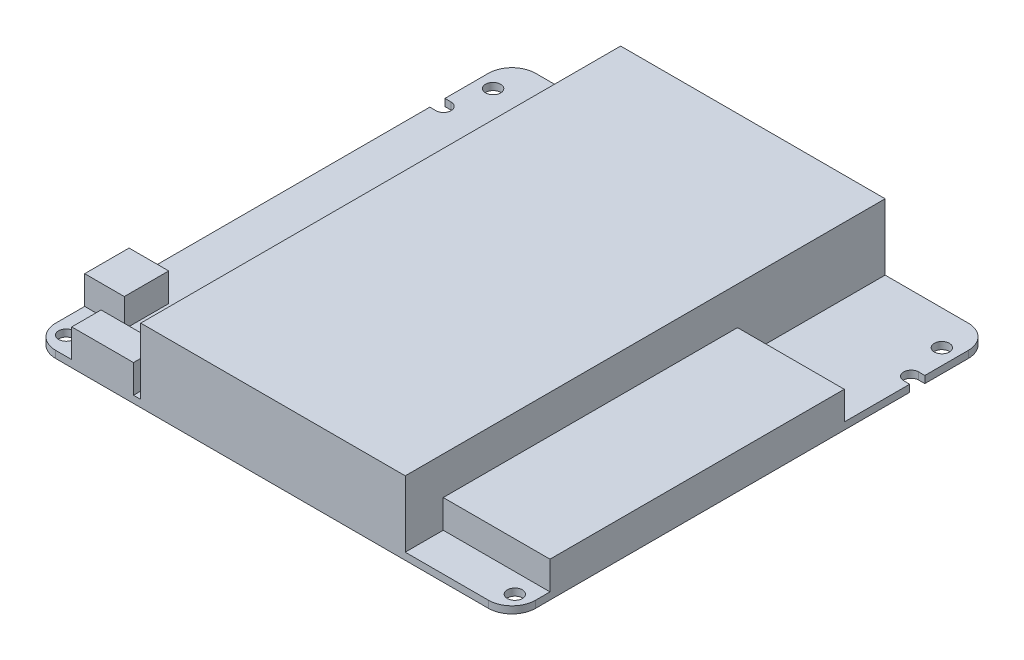
SolidWorks part; units mm, degrees
ref_plane "Спереди" through (0, 0, 0) normal (0, 0, 1) x (1, 0, 0)
ref_plane "Сверху" through (0, 0, 0) normal (0, 1, 0) x (1, 0, 0)
ref_plane "Справа" through (0, 0, 0) normal (1, 0, 0) x (0, 0, -1)
sketch "Эскиз1" plane through (0, 0, 0) normal (0, 1, 0) x (1, 0, 0)
  line L0 (-62.5901, -46.9) -> (98.0952, -46.9) construction
  line L1 (-45.8, 50.8) -> (45.8, 50.8)
  line L2 (-50.8, 45.8) -> (-50.8, -45.8)
  line L3 (-45.8, -50.8) -> (45.8, -50.8)
  line L4 (50.8, 45.8) -> (50.8, -45.8)
  line L5 (-50.8, 50.8) -> (50.8, -50.8) construction
  line L6 (-50.8, -50.8) -> (50.8, 50.8) construction
  line L7 (-47.5, 92.2985) -> (-47.5, -70.4765) construction
  line L8 (47.5, 92.2985) -> (47.5, -70.4765) construction
  line L9 (-85.2704, 43.5) -> (74.0758, 43.5) construction
  line L10 (-65.9548, 35) -> (74.0758, 35) construction
  line L11 (-49.5, 37.9623) -> (-49.5, 31.6688) construction
  line L12 (49.5, 37.9623) -> (49.5, 31.6688) construction
  line L14 (-49.5, 36.6) -> (-50.8, 36.6)
  line L16 (-49.5, 33.4) -> (-50.8, 33.4)
  line L17 (-50.8, 36.6) -> (-50.8, 33.4)
  line L18 (49.5, 36.6) -> (50.8, 36.6)
  line L20 (49.5, 33.4) -> (50.8, 33.4)
  line L21 (50.8, 36.6) -> (50.8, 33.4)
  arc A0 (45.8, 50.8) -> (50.8, 45.8) centre (45.8, 45.8) cw
  arc A1 (50.8, -45.8) -> (45.8, -50.8) centre (45.8, -45.8) cw
  arc A2 (-45.8, -50.8) -> (-50.8, -45.8) centre (-45.8, -45.8) cw
  arc A3 (-50.8, 45.8) -> (-45.8, 50.8) centre (-45.8, 45.8) cw
  circle A4 centre (-47.5, -46.9) radius 1.6
  circle A5 centre (47.5, -46.9) radius 1.6
  circle A6 centre (47.5, 43.5) radius 1.6
  circle A7 centre (-47.5, 43.5) radius 1.6
  arc A8 (-49.5, 33.4) -> (-49.5, 36.6) centre (-49.5, 35) ccw
  arc A9 (49.5, 36.6) -> (49.5, 33.4) centre (49.5, 35) ccw
  point P0 (0, 0)
  dimension "D3" = 5
  dimension "D8" = 3.2
  dimension "D9" = 8.5
  dimension "D1" = 101.6
  dimension "D2" = 101.6
  dimension "D4" = 3.3
  dimension "D5" = 95
  dimension "D6" = 7.3
  dimension "D7" = 90.4
  dimension "D10" = 1.3
  dimension "D11" = 99
extrude "Бобышка-Вытянуть1" add sketch "Эскиз1" along normal blind 1.5 contours A9 L18 L4 A0 L1 A3 L2 L14 A8 L16 A2 L3 A1 L20 A7 A6 A5 A4 region at (0, 0, 0.0505)
sketch "Эскиз2" plane through (0, 1.5, 0) normal (0, 1, 0) x (1, 0, 0)
  line L0 (-45.8, 50.8) -> (45.8, 50.8) construction
  line L1 (-27.8, 50.8) -> (28.2, 50.8)
  line L2 (-27.8, 50.8) -> (-27.8, -50.8)
  line L3 (-27.8, -50.8) -> (28.2, -50.8)
  line L4 (28.2, 50.8) -> (28.2, -50.8)
  line L5 (-45.8, -50.8) -> (45.8, -50.8) construction
  dimension "D1" = 23
  dimension "D2" = 56
extrude "Бобышка-Вытянуть2" add sketch "Эскиз2" along normal blind 14
sketch "Эскиз3" plane through (0, 1.5, 0) normal (0, 1, 0) x (1, 0, 0)
  line L0 (28.2, -50.8) -> (28.2, 50.8) construction
  line L1 (28.2, 19.545) -> (50.8, 19.545)
  line L2 (28.2, 19.545) -> (28.2, -42.7592)
  line L3 (28.2, -42.7592) -> (50.8, -42.7592)
  line L4 (50.8, 19.545) -> (50.8, -42.7592)
  line L5 (50.8, 33.4) -> (50.8, -45.8) construction
  line L6 (-45.8, -50.8) -> (-27.8, -50.8) construction
  line L7 (-42.4088, -50.8) -> (-29.3358, -50.8)
  line L8 (-42.4088, -50.8) -> (-42.4088, -44.5816)
  line L9 (-42.4088, -44.5816) -> (-29.3358, -44.5816)
  line L10 (-29.3358, -50.8) -> (-29.3358, -44.5816)
  line L11 (-50.8, 33.4) -> (-50.8, -45.8) construction
  line L12 (-50.8, -39.6706) -> (-42.4088, -39.6706)
  line L13 (-50.8, -39.6706) -> (-50.8, -30.2711)
  line L14 (-50.8, -30.2711) -> (-42.4088, -30.2711)
  line L15 (-42.4088, -39.6706) -> (-42.4088, -30.2711)
extrude "Бобышка-Вытянуть3" add sketch "Эскиз3" along normal blind 6
sketch "Эскиз4" plane through (0, 0, 0) normal (0, -1, 0) x (1, 0, 0)
  line L0 (-45.8, -50.8) -> (45.8, -50.8) construction
  line L1 (30.8, -50.8) -> (24.8, -50.8)
  line L2 (30.8, -50.8) -> (30.8, -39.5)
  line L3 (30.8, -39.5) -> (24.8, -39.5)
  line L4 (24.8, -50.8) -> (24.8, -39.5)
  line L5 (50.8, -45.8) -> (50.8, -36.6) construction
  dimension "D1" = 20
  dimension "D2" = 11.3
  dimension "D3" = 6
extrude "Бобышка-Вытянуть4" add sketch "Эскиз4" along normal blind 13.4
